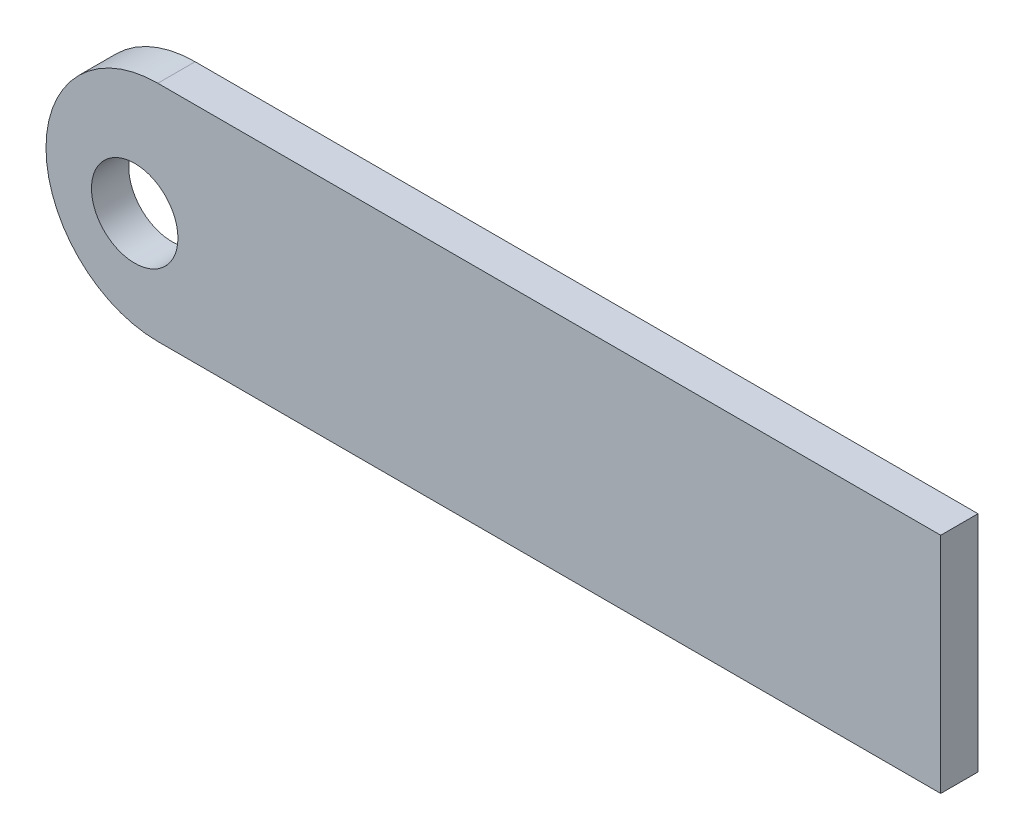
SolidWorks part; units mm, degrees
material "6061-T6 (SS)"
ref_plane "Front" through (0, 0, 0) normal (0, 0, 1) x (1, 0, 0)
ref_plane "Top" through (0, 0, 0) normal (0, 1, 0) x (1, 0, 0)
ref_plane "Right" through (0, 0, 0) normal (1, 0, 0) x (0, 0, -1)
sketch "Sketch1" plane through (0, 0, 0) normal (0, 0, 1) x (1, 0, 0)
  line L1 (0, 0) -> (76.2, 0)
  line L2 (0, 0) -> (0, 19.05)
  line L3 (0, 19.05) -> (76.2, 19.05)
  line L4 (76.2, 0) -> (76.2, 19.05)
  line L5 (0, 0) -> (76.2, 19.05) construction
  line L6 (0, 19.05) -> (76.2, 0) construction
  point P4 (38.1, 9.525)
  dimension "D1" = 19.05
  dimension "D2" = 76.2
extrude "Boss-Extrude1" add sketch "Sketch1" along normal blind 3.175
fillet "Fillet1" radius 9.525 2 edges at (0, 0, 1.5875) (0, 19.05, 1.5875)
sketch "Sketch2" plane through (0, 0, 3.175) normal (0, 0, 1) x (1, 0, 0)
  circle A1 centre (7.5535, 8.4737) radius 3.683
extrude "Cut-Extrude1" cut sketch "Sketch2" against normal through all
